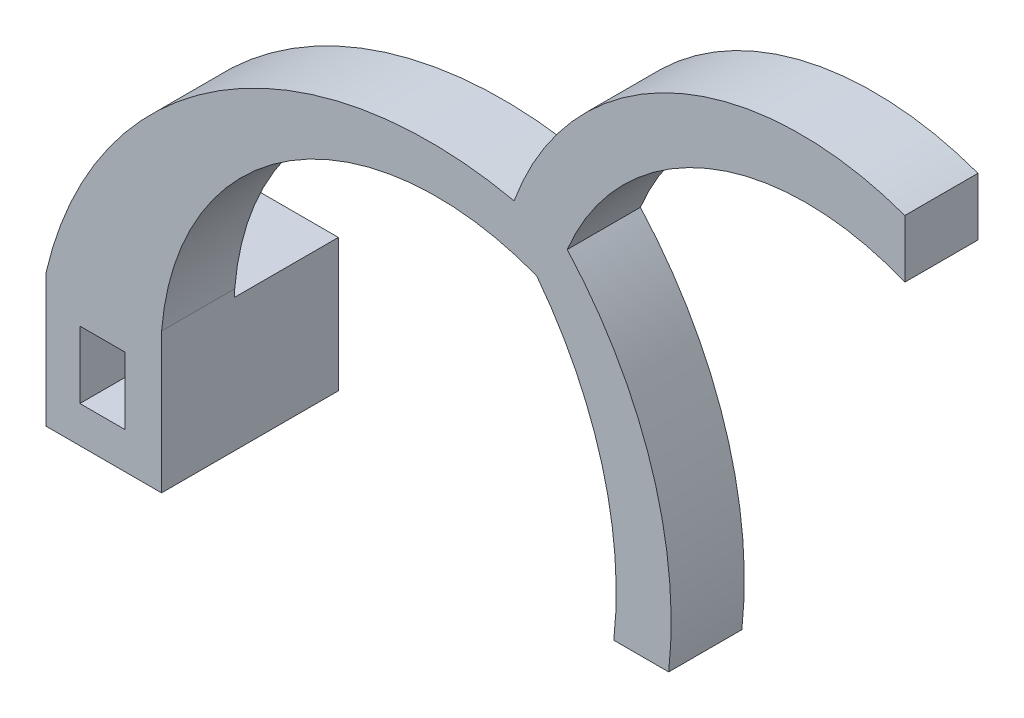
SolidWorks part; units mm, degrees
ref_plane "Front Plane" through (0, 0, 0) normal (0, 0, 1) x (1, 0, 0)
ref_plane "Top Plane" through (0, 0, 0) normal (0, 1, 0) x (1, 0, 0)
ref_plane "Right Plane" through (0, 0, 0) normal (1, 0, 0) x (0, 0, -1)
sketch "Sketch1" plane through (0, 0, 0) normal (0, 0, 1) x (1, 0, 0)
  line L1 (-1.85, 2.75) -> (1.85, 2.75)
  line L2 (-1.85, 2.75) -> (-1.85, -2.75)
  line L3 (-1.85, -2.75) -> (1.85, -2.75)
  line L4 (1.85, 2.75) -> (1.85, -2.75)
  line L6 (4.85, 5.75) -> (4.85, -5.75)
  line L7 (4.85, -5.75) -> (-4.629, -5.75)
  line L8 (-4.629, -5.75) -> (-4.629, 5.1487)
  line L18 (41.939, 2.3297) -> (46.4408, 2.3297)
  arc A8 (4.85, 5.75) -> (35.6199, 25.0444) centre (27.4227, 3.9345) cw
  arc A10 (46.4408, 2.3297) -> (38.1232, 28.1736) centre (13.4632, 5.9766) ccw
  arc A11 (41.939, 2.3297) -> (35.6199, 25.0444) centre (10.5958, 5.8465) ccw
  arc A12 (-4.629, 5.1487) -> (38.1232, 28.1736) centre (26.8654, -2.1264) cw
  point P4 (0, 2.75)
  point P6 (-1.85, 0)
  dimension "D1" = 5.5
  dimension "D2" = 3.7
  dimension "D3" = 41.939
  dimension "D4" = 3
  dimension "D5" = 3
  dimension "D6" = 19.2944
  dimension "D7" = 6.3191
extrude "Boss-Extrude1" add sketch "Sketch1" along normal blind 6
sketch "Sketch2" plane through (0, 0, 6) normal (0, 0, 1) x (1, 0, 0)
  line L0 (0, 2.75) -> (0, -2.75) construction
  line L1 (1.85, 2.75) -> (-1.85, 2.75) construction
  line L2 (-1.85, -2.75) -> (1.85, -2.75) construction
  line L3 (-1.85, 0) -> (1.85, 0) construction
  line L4 (-1.85, 2.75) -> (-1.85, -2.75) construction
  line L5 (1.85, -2.75) -> (1.85, 2.75) construction
sketch "Sketch3" plane through (0, 0, 0) normal (0, 0, 1) x (1, 0, 0)
  line L1 (-4.629, -5.75) -> (4.85, -5.75)
  line L2 (-4.629, -5.75) -> (-4.629, 5.1487)
  line L3 (-4.629, 5.1487) -> (4.85, 5.1487)
  line L4 (4.85, -5.75) -> (4.85, 5.1487)
  line L5 (-1.85, 2.75) -> (1.85, 2.75)
  line L6 (-1.85, 2.75) -> (-1.85, -2.75)
  line L7 (-1.85, -2.75) -> (1.85, -2.75)
  line L8 (1.85, 2.75) -> (1.85, -2.75)
  point P12 (0, 0)
extrude "Boss-Extrude2" add sketch "Sketch3" against normal blind 8.5
sketch "Sketch4" plane through (0, 0, 0) normal (0, 0, 1) x (1, 0, 0)
  line L1 (65.8084, 44.4352) -> (65.8084, 39.6952)
  arc A2 (38.1232, 28.1736) -> (-4.629, 5.1487) centre (26.8654, -2.1264) ccw construction
  arc A3 (33.7627, 29.4529) -> (38.1232, 28.1736) centre (26.8654, -2.1264) cw
  arc A4 (38.1232, 28.1736) -> (65.8084, 39.6952) centre (57.7267, 20.0918) cw
  arc A5 (65.8084, 44.4352) -> (33.7627, 29.4529) centre (57.2767, 20.9212) ccw
extrude "Boss-Extrude3" add sketch "Sketch4" along normal through all
